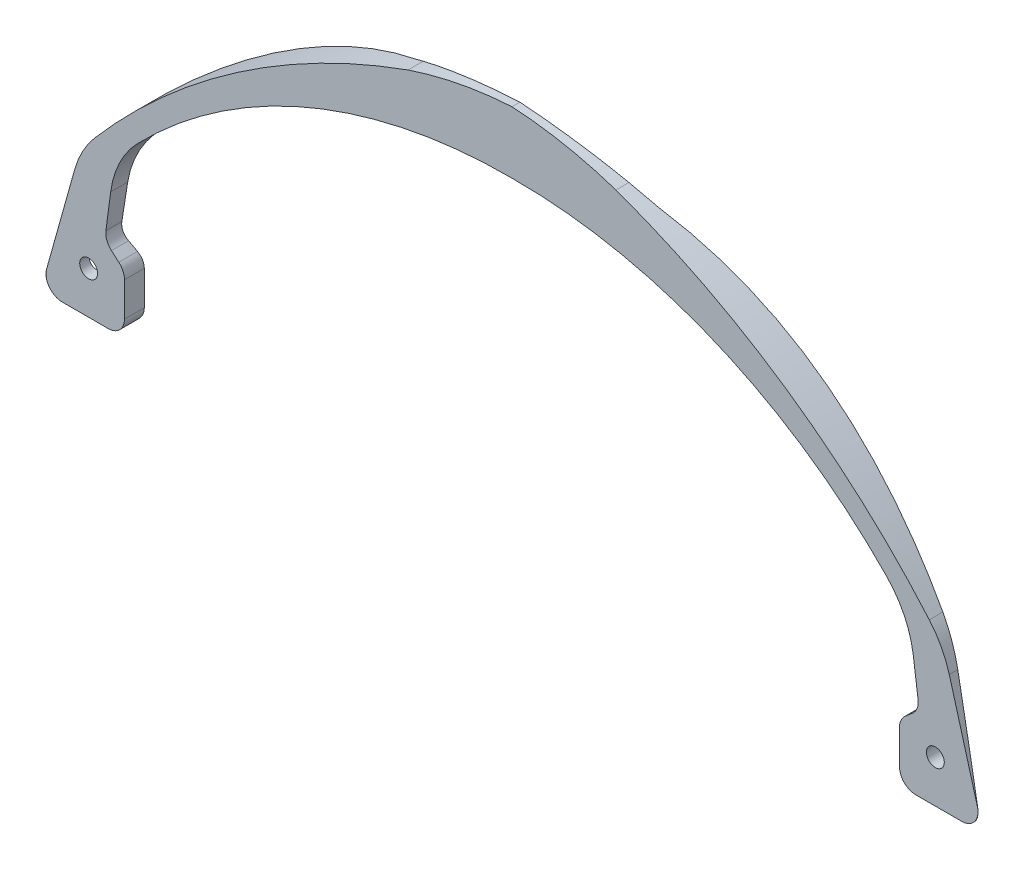
SolidWorks part; units mm, degrees
ref_plane "Plan de face" through (0, 0, 0) normal (0, 0, 1) x (1, 0, 0)
ref_plane "Plan de dessus" through (0, 0, 0) normal (0, 1, 0) x (1, 0, 0)
ref_plane "Plan de droite" through (0, 0, 0) normal (1, 0, 0) x (0, 0, -1)
sketch "Esquisse1" plane through (0, 0, 0) normal (0, 0, 1) x (1, 0, 0)
  line L0 (0, 108) -> (0, 0)
  line L1 (0, 0) -> (-130, 0)
  dimension "D1" = 108
  dimension "D2" = 130
ref_axis "Axe1" through (0, 108, 0) along (0, -1, 0)
ref_axis "Axe2" through (0, 0, 0) along (-1, 0, 0)
sketch "Esquisse3" plane through (0, 0, 0) normal (0, 0, 1) x (1, 0, 0)
  line L0 (0, 108) -> (0, 0) construction
  line L1 (0, 0) -> (-130, 0) construction
  point P0 (-119, 35)
  dimension "D1" = 119
  dimension "D2" = 35
sketch "Esquisse2" plane through (0, 0, 0) normal (0, 0, 1) x (1, 0, 0)
  line L0 (0, 108) -> (0, 0) construction
  line L1 (-125.0643, 10) -> (-122, 33)
  line L2 (0, 0) -> (-130, 0) construction
  line L3 (-125.0643, 10) -> (-119, 4.7823)
  line L4 (-119, 4.7823) -> (-119, -13)
  line L5 (-119, -13) -> (-144.7, -13)
  line L6 (-144.7, -13) -> (-132.5643, 30.3327)
  line L7 (0, 108) -> (0, 89)
  circle A0 centre (-130, 0) radius 2.75
  arc A1 (-31.9184, 101.8188) -> (-132.5643, 30.3327) centre (45.2497, -113.4201) ccw
  arc A3 (0, 89) -> (-122, 33) centre (-0.8451, -70.0518) ccw
  arc A5 (-31.9184, 101.8188) -> (0, 108) centre (7.063, -13.9727) cw
  dimension "D1" = 5.5
  dimension "D2" = 89
  dimension "D3" = 10
  dimension "D4" = 119
  dimension "D5" = 25.7
  dimension "D6" = 122
  dimension "D7" = 8
  dimension "D8" = 13
  dimension "D9" = 33
  dimension "D10" = 132.5643
extrude "Boss.-Extru.1" add sketch "Esquisse2" along normal blind 12
sketch "Esquisse5" plane through (-130.8003, 36.6317, 0) normal (-0.9629, 0.2697, 0) x (0, 0, 1)
  line L2 (12, -6.5413) -> (0, -6.5413) construction
  line L3 (2, -6.5413) -> (12, -6.5413)
  line L4 (12, -6.5413) -> (12, -51.5413)
  line L6 (12, -51.5413) -> (2, -6.5413)
  dimension "D2" = 2
fillet "Congé1" radius 30 1 edges at (-132.5643, 30.3327, 6)
fillet "Congé2" radius 30 1 edges at (-122, 33, 6)
fillet "Congé3" radius 5 1 edges at (-125.0643, 10, 6)
fillet "Congé4" radius 5 1 edges at (-119, 4.7823, 6)
fillet "Congé5" radius 5 1 edges at (-119, -13, 6)
fillet "Congé6" radius 5 1 edges at (-144.7, -13, 6)
mirror "Symétrie1" about plane through (0, 108, 12) normal (-1, 0, 0) of "Congé6", "Congé5", "Congé4", "Congé3", "Congé2", "Congé1", "Boss.-Extru.1"
ref_plane "Plan1" through (0, 108, 0) normal (0, 1, 0) x (1, 0, 0)
sketch "Esquisse9" plane through (0, 108, 0) normal (0, 1, 0) x (1, 0, 0)
  line L0 (0, -12) -> (0, 0) construction
  line L4 (143.1073, -12) -> (143.1073, 0) construction
  line L6 (134.2944, -12) -> (142.9221, -12) construction
  line L7 (-132.5643, -12) -> (-144.7, -12) construction
  line L11 (31.9184, -12) -> (128.1573, -12) construction
  line L12 (143.1073, -12) -> (143.1073, 11.6864)
  line L13 (143.1073, 11.6864) -> (-142.9221, 11.6864)
  line L14 (-142.9221, 11.6864) -> (-142.9221, -12)
  line L15 (-128.1573, -12) -> (-31.9184, -12) construction
  arc A7 (40, -7) -> (143.1073, -12) centre (82.2235, -201.9009) cw
  arc A8 (40, -7) -> (-34.3331, -7) centre (2.8334, 259.4993) cw
  arc A9 (-34.3331, -7) -> (-142.9221, -12) centre (-79.2975, -212.1297) ccw
  dimension "D2" = 0
  dimension "D3" = 5
  dimension "D5" = 0
  dimension "D6" = 0
  dimension "D7" = 0
  dimension "D10" = 40
  dimension "D11" = 5
extrude "Enlèv. mat.-Extru.6" cut sketch "Esquisse9" against normal blind 153
